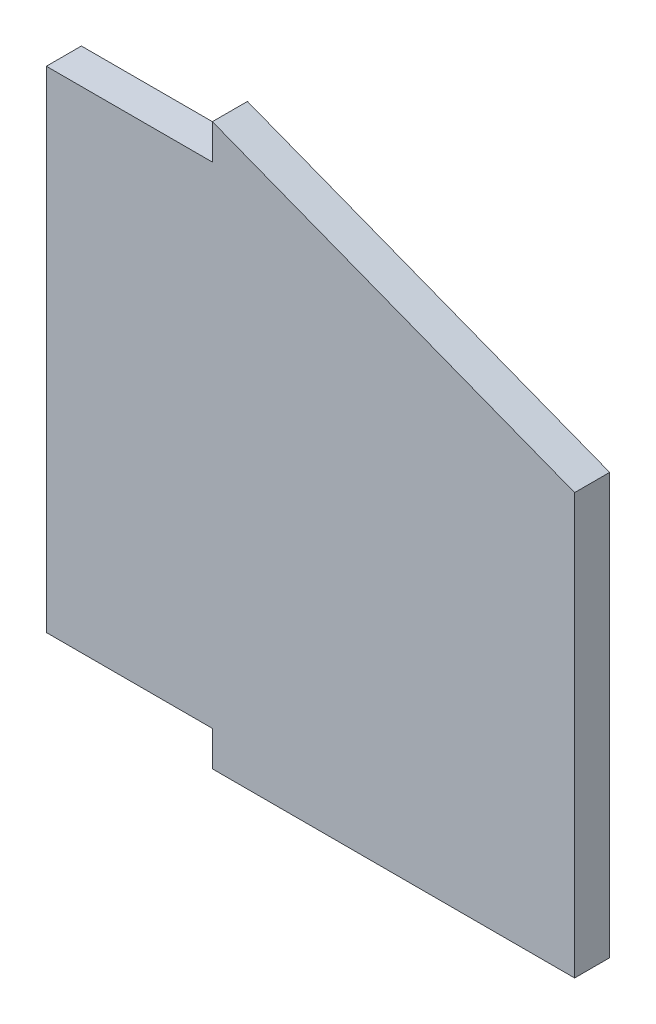
SolidWorks part; units mm, degrees
other "Markup1"
sketch "Sketch2" plane through (0, -5, 5) normal (-0.9994, -0.0223, 0.0275) x (0.021, 0.2509, 0.9678)
ref_plane "Front Plane" through (0, 0, 0) normal (0, 0, 1) x (1, 0, 0)
ref_plane "Top Plane" through (0, 0, 0) normal (0, 1, 0) x (1, 0, 0)
ref_plane "Right Plane" through (0, 0, 0) normal (1, 0, 0) x (0, 0, -1)
sketch "Sketch1" plane through (0, 0, 0) normal (0, 0, 1) x (1, 0, 0)
  line L0 (0, 0) -> (0, 70)
  line L1 (0, 70) -> (23.7, 70)
  line L5 (75.4, -5) -> (23.7, -5)
  line L6 (23.7, -5) -> (23.7, 0)
  line L7 (23.7, 0) -> (0, 0)
  line L8 (23.7, 70) -> (23.7, 75)
  line L9 (23.7, 75) -> (75.4, 55)
  line L10 (75.4, 55) -> (75.4, -5)
  line L11 (23.7, 75) -> (23.7, -5) construction
  point P3 (23.7, 35)
  point P10 (0, 35)
  dimension "D1" = 80
  dimension "D2" = 60
  dimension "D3" = 51.7
  dimension "D4" = 23.7
  dimension "D5" = 70
extrude "Boss-Extrude1" add sketch "Sketch1" along normal blind 5
